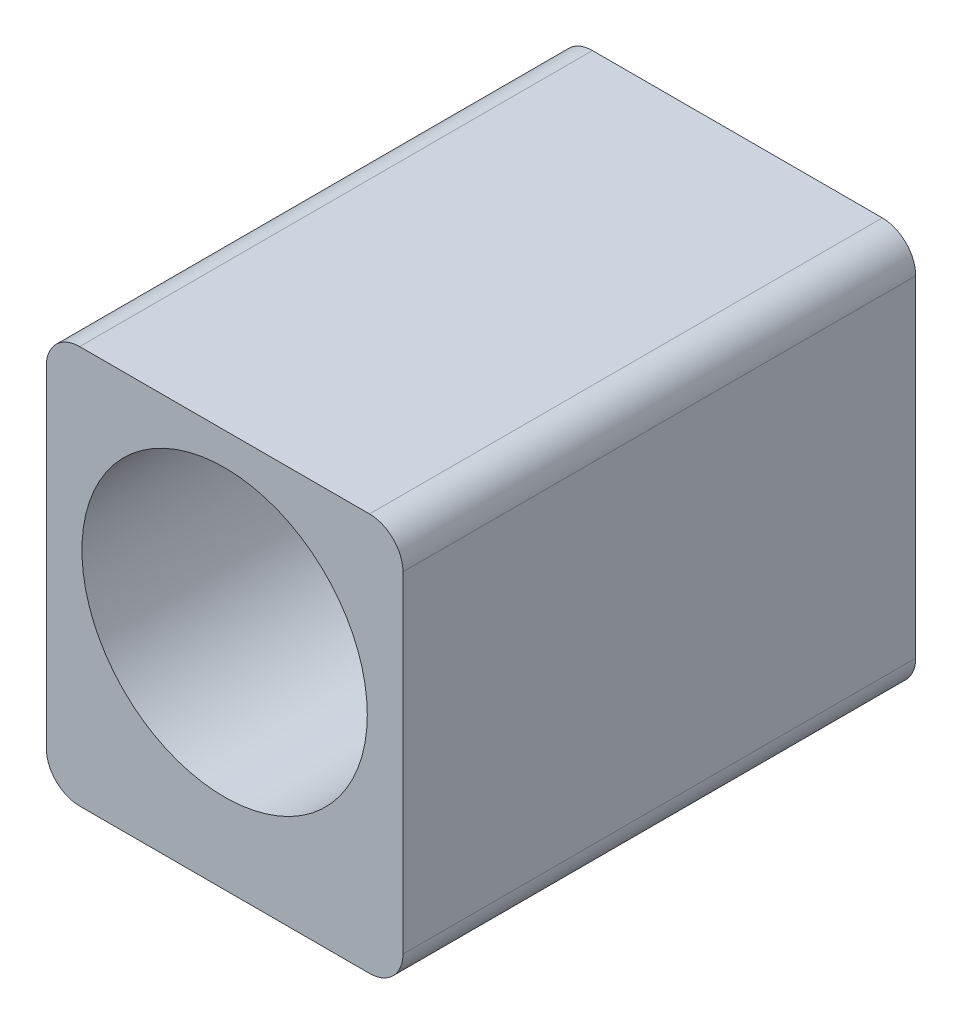
SolidWorks part; units mm, degrees
ref_plane "Front Plane" through (0, 0, 0) normal (0, 0, 1) x (1, 0, 0)
ref_plane "Top Plane" through (0, 0, 0) normal (0, 1, 0) x (1, 0, 0)
ref_plane "Right Plane" through (0, 0, 0) normal (1, 0, 0) x (0, 0, -1)
sketch "Sketch1" plane through (0, 0, 0) normal (0, 0, 1) x (1, 0, 0)
  line L0 (-13, -19.999) -> (13, -19.999)
  line L1 (16, -16.999) -> (16, 12.7)
  line L2 (13, 15.7) -> (-13, 15.7)
  line L3 (-16, 12.7) -> (-16, -16.999)
  arc A0 (13, -19.999) -> (16, -16.999) centre (13, -16.999) ccw
  arc A1 (16, 12.7) -> (13, 15.7) centre (13, 12.7) ccw
  arc A2 (-13, 15.7) -> (-16, 12.7) centre (-13, 12.7) ccw
  arc A3 (-16, -16.999) -> (-13, -19.999) centre (-13, -16.999) ccw
  circle A4 centre (0, 0) radius 12.8
extrude "Boss-Extrude1" add sketch "Sketch1" along normal mid plane 46
ref_plane "Plane1" through (0, -19.999, 0) normal (0, 1, 0) x (1, 0, 0)
sketch "Sketch2" plane through (0, -19.999, 0) normal (0, 1, 0) x (1, 0, 0)
  circle A0 centre (12, -17.5) radius 2
  circle A1 centre (-12, 17.5) radius 2
extrude "Cut-Extrude1" cut sketch "Sketch2" along normal blind 7.5
